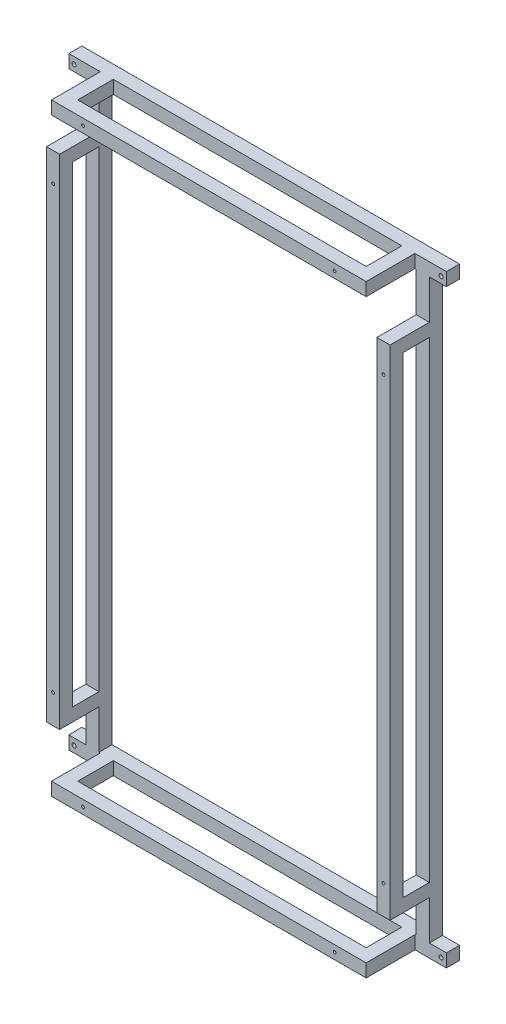
SolidWorks part; units mm, degrees
ref_plane "Plan de face" through (0, 0, 0) normal (0, 0, 1) x (1, 0, 0)
ref_plane "Plan de dessus" through (0, 0, 0) normal (0, 1, 0) x (1, 0, 0)
ref_plane "Plan de droite" through (0, 0, 0) normal (1, 0, 0) x (0, 0, -1)
sketch "Esquisse1" plane through (0, 0, 0) normal (0, 0, 1) x (1, 0, 0)
  line L1 (0, 0) -> (720, 0)
  line L2 (0, 0) -> (0, 25)
  line L3 (0, 25) -> (720, 25)
  line L4 (720, 0) -> (720, 25)
  line L5 (720, -1100) -> (0, -1100)
  line L6 (720, -1100) -> (720, -1125)
  line L7 (720, -1125) -> (0, -1125)
  line L8 (0, -1100) -> (0, -1125)
  point P9 (720, -1112.5)
  point P10 (720, 12.5)
  dimension "D1" = 25
  dimension "D2" = 720
  dimension "D3" = 720
  dimension "D4" = 0
  dimension "D5" = 25
  dimension "D6" = 1100
extrude "Boss.-Extru.1" add sketch "Esquisse1" along normal blind 25
sketch "Esquisse2" plane through (0, 0, 25) normal (0, 0, 1) x (1, 0, 0)
  line L0 (0, 25) -> (0, 0) construction
  line L1 (720, 0) -> (720, 25) construction
  line L2 (720, 25) -> (0, 25) construction
  line L4 (720, -1125) -> (720, -1100) construction
  line L5 (0, -1125) -> (720, -1125) construction
  line L6 (0, -1100) -> (0, -1125) construction
  circle A0 centre (10, 12.5) radius 4
  circle A1 centre (710, 12.5) radius 4
  circle A2 centre (710, -1112.5) radius 4
  circle A3 centre (10, -1112.5) radius 4
  point P22 (7.912, -1225)
  point P23 (0, 0)
  dimension "D2" = 8
  dimension "D3" = 8
  dimension "D7" = 8
  dimension "D8" = 8
  dimension "D1" = 700
  dimension "D4" = 10
  dimension "D5" = 10
  dimension "D6" = 12.5
  dimension "D9" = 10
  dimension "D10" = 12.5
  dimension "D11" = 10
  dimension "D12" = 12.5
extrude "Enlèv. mat.-Extru.1" cut sketch "Esquisse2" against normal blind 100 and the other way blind 25
sketch "Esquisse3" plane through (0, 0, 25) normal (0, 0, 1) x (1, 0, 0)
  line L0 (720, 25) -> (0, 25) construction
  line L1 (60, 25) -> (85, 25)
  line L2 (60, 25) -> (60, 0)
  line L3 (60, 0) -> (85, 0)
  line L4 (85, 25) -> (85, 0)
  line L5 (0, 0) -> (720, 0) construction
  line L6 (0, 25) -> (0, 0) construction
  line L7 (635, 0) -> (660, 0)
  line L8 (635, 0) -> (635, 25)
  line L9 (635, 25) -> (660, 25)
  line L10 (660, 0) -> (660, 25)
  line L11 (720, 0) -> (720, 25) construction
  line L12 (0, -1125) -> (720, -1125) construction
  line L13 (60, -1125) -> (85, -1125)
  line L14 (60, -1125) -> (60, -1100)
  line L15 (60, -1100) -> (85, -1100)
  line L16 (85, -1125) -> (85, -1100)
  line L17 (720, -1100) -> (0, -1100) construction
  line L19 (660, -1100) -> (635, -1100)
  line L20 (660, -1100) -> (660, -1125)
  line L21 (660, -1125) -> (635, -1125)
  line L22 (635, -1100) -> (635, -1125)
  point P16 (635, 12.5)
  dimension "D1" = 25
  dimension "D2" = 25
  dimension "D3" = 60
  dimension "D4" = 60
  dimension "D5" = 550
extrude "Boss.-Extru.2" add sketch "Esquisse3" along normal blind 68
sketch "Esquisse4" plane through (0, 0, 93) normal (0, 0, 1) x (1, 0, 0)
  line L1 (660, 25) -> (60, 25)
  line L2 (660, 25) -> (660, 0)
  line L3 (660, 0) -> (60, 0)
  line L4 (60, 25) -> (60, 0)
  line L5 (60, -1125) -> (660, -1125)
  line L6 (60, -1125) -> (60, -1100)
  line L7 (60, -1100) -> (660, -1100)
  line L8 (660, -1125) -> (660, -1100)
extrude "Boss.-Extru.3" add sketch "Esquisse4" along normal blind 25
sketch "Esquisse5" plane through (0, 0, 118) normal (0, 0, 1) x (1, 0, 0)
  line L0 (60, 0) -> (660, 0) construction
  line L1 (0, 25) -> (0, 0) construction
  line L2 (60, -1125) -> (660, -1125) construction
  line L3 (0, -1100) -> (0, -1125) construction
  line L4 (720, -1125) -> (720, -1100) construction
  circle A0 centre (120, 12.5) radius 2.75
  circle A1 centre (600, 12.5) radius 2.75
  circle A2 centre (600, -1112.5) radius 2.75
  circle A3 centre (120, -1112.5) radius 2.75
  dimension "D1" = 5.5
  dimension "D2" = 5.5
  dimension "D7" = 5.5
  dimension "D8" = 5.5
  dimension "D3" = 12.5
  dimension "D4" = 12.5
  dimension "D5" = 480
  dimension "D6" = 120
  dimension "D9" = 12.5
  dimension "D10" = 12.5
  dimension "D11" = 120
  dimension "D12" = 120
extrude "Enlèv. mat.-Extru.2" cut sketch "Esquisse5" against normal blind 25
sketch "Esquisse6" plane through (0, 0, 0) normal (0, 0, -1) x (-1, 0, 0)
  line L0 (-720, -1100) -> (0, -1100) construction
  line L1 (-687.5, -1100) -> (-662.5, -1100)
  line L2 (-687.5, -1100) -> (-687.5, 0)
  line L3 (-687.5, 0) -> (-662.5, 0)
  line L4 (-662.5, -1100) -> (-662.5, 0)
  line L5 (0, 0) -> (-720, 0) construction
  line L6 (-720, -1125) -> (-720, -1100) construction
  line L7 (-57.5, 0) -> (-32.5, 0)
  line L8 (-57.5, 0) -> (-57.5, -1100)
  line L9 (-57.5, -1100) -> (-32.5, -1100)
  line L10 (-32.5, 0) -> (-32.5, -1100)
  line L11 (0, -1100) -> (0, -1125) construction
  point P12 (-675, -1100)
  point P13 (-45, -1100)
  point P16 (-720, -1112.5)
  dimension "D1" = 25
  dimension "D2" = 25
  dimension "D3" = 630
  dimension "D4" = 45
  dimension "D5" = 45
extrude "Boss.-Extru.4" add sketch "Esquisse6" against normal blind 25
sketch "Esquisse7" plane through (0, 0, 25) normal (0, 0, 1) x (1, 0, 0)
  line L0 (32.5, -1100) -> (32.5, 0) construction
  line L1 (32.5, -1025) -> (57.5, -1025)
  line L2 (32.5, -1025) -> (32.5, -1000)
  line L3 (32.5, -1000) -> (57.5, -1000)
  line L4 (57.5, -1025) -> (57.5, -1000)
  line L5 (57.5, 0) -> (57.5, -1100) construction
  line L6 (662.5, -1100) -> (662.5, 0) construction
  line L7 (32.5, -100) -> (57.5, -100)
  line L8 (32.5, -100) -> (32.5, -75)
  line L9 (32.5, -75) -> (57.5, -75)
  line L10 (57.5, -100) -> (57.5, -75)
  line L11 (662.5, -100) -> (687.5, -100)
  line L12 (662.5, -100) -> (662.5, -75)
  line L13 (662.5, -75) -> (687.5, -75)
  line L14 (687.5, -100) -> (687.5, -75)
  line L15 (687.5, 0) -> (687.5, -1100) construction
  line L16 (660, -1125) -> (720, -1125) construction
  line L17 (662.5, -1025) -> (687.5, -1025)
  line L18 (662.5, -1025) -> (662.5, -1000)
  line L19 (662.5, -1000) -> (687.5, -1000)
  line L20 (687.5, -1025) -> (687.5, -1000)
  line L21 (720, 25) -> (660, 25) construction
  line L22 (0, -1125) -> (60, -1125) construction
  line L23 (60, 25) -> (0, 25) construction
  point P24 (675, -75)
  point P25 (32.5, -1012.5)
  point P26 (32.5, -87.5)
  point P27 (687.5, -1012.5)
  point P28 (687.5, -87.5)
  point P33 (690, 25)
  dimension "D1" = 25
  dimension "D2" = 25
  dimension "D3" = 25
  dimension "D4" = 25
  dimension "D5" = 925
  dimension "D6" = 925
  dimension "D7" = 1150
  dimension "D8" = 112.5
  dimension "D9" = 112.5
  dimension "D10" = 112.5
  dimension "D11" = 112.5
extrude "Boss.-Extru.5" add sketch "Esquisse7" along normal blind 50
sketch "Esquisse8" plane through (0, 0, 75) normal (0, 0, 1) x (1, 0, 0)
  line L1 (687.5, -1025) -> (662.5, -1025)
  line L2 (687.5, -1025) -> (687.5, -75)
  line L3 (687.5, -75) -> (662.5, -75)
  line L4 (662.5, -1025) -> (662.5, -75)
  line L5 (32.5, -75) -> (57.5, -75)
  line L6 (32.5, -75) -> (32.5, -1025)
  line L7 (32.5, -1025) -> (57.5, -1025)
  line L8 (57.5, -75) -> (57.5, -1025)
extrude "Boss.-Extru.6" add sketch "Esquisse8" along normal blind 25
sketch "Esquisse9" plane through (0, 0, 100) normal (0, 0, 1) x (1, 0, 0)
  line L0 (660, -1125) -> (720, -1125) construction
  line L1 (720, 25) -> (660, 25) construction
  line L2 (60, 25) -> (0, 25) construction
  line L3 (0, -1125) -> (60, -1125) construction
  line L4 (662.5, -75) -> (662.5, -1025) construction
  line L5 (57.5, -1025) -> (57.5, -75) construction
  line L6 (32.5, -75) -> (32.5, -1025) construction
  circle A0 centre (675, -970) radius 2.75
  circle A1 centre (45, -970) radius 2.75
  circle A2 centre (675, -130) radius 2.75
  circle A3 centre (45, -130) radius 2.75
  point P12 (690, 25)
  dimension "D1" = 5.5
  dimension "D2" = 5.5
  dimension "D3" = 5.5
  dimension "D4" = 5.5
  dimension "D5" = 840
  dimension "D6" = 840
  dimension "D7" = 1150
  dimension "D8" = 155
  dimension "D9" = 155
  dimension "D10" = 155
  dimension "D11" = 155
  dimension "D12" = 12.5
  dimension "D13" = 12.5
  dimension "D14" = 12.5
  dimension "D15" = 12.5
extrude "Enlèv. mat.-Extru.3" cut sketch "Esquisse9" against normal blind 25
